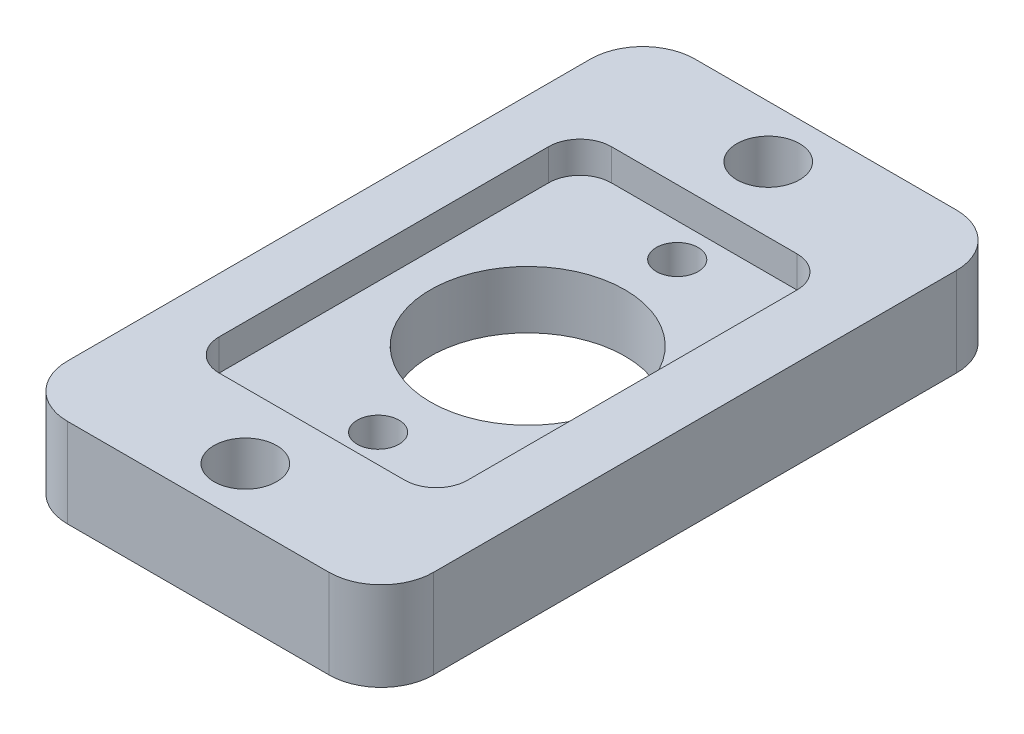
SolidWorks part; units mm, degrees
ref_plane "Front Plane" through (0, 0, 0) normal (0, 0, 1) x (1, 0, 0)
ref_plane "Top Plane" through (0, 0, 0) normal (0, 1, 0) x (1, 0, 0)
ref_plane "Right Plane" through (0, 0, 0) normal (1, 0, 0) x (0, 0, -1)
sketch "Sketch1" plane through (0, 0, 0) normal (0, 1, 0) x (1, 0, 0)
  line L1 (2, 0) -> (12, 0)
  line L2 (0, -2) -> (0, -22)
  line L3 (2, -24) -> (12, -24)
  line L4 (14, -2) -> (14, -22)
  arc A0 (0, -22) -> (2, -24) centre (2, -22) ccw
  arc A1 (12, -24) -> (14, -22) centre (12, -22) ccw
  arc A2 (12, 0) -> (14, -2) centre (12, -2) cw
  arc A3 (2, 0) -> (0, -2) centre (2, -2) ccw
  point P7 (0, -24)
  point P12 (14, 0)
  point P15 (0, 0)
  dimension "D3" = 2
  dimension "D1" = 14
  dimension "D2" = 24
extrude "Boss-Extrude1" add sketch "Sketch1" along normal blind 3.4
sketch "Sketch2" plane through (0, 3.4, 0) normal (0, 1, 0) x (1, 0, 0)
  line L0 (12, 0) -> (2, 0) construction
  line L1 (3.3, -4.5) -> (10.4, -4.5)
  line L2 (2.1, -5.7) -> (2.1, -18.3)
  line L3 (3.3, -19.5) -> (10.4, -19.5)
  line L4 (11.6, -5.7) -> (11.6, -18.3)
  line L5 (14, -22) -> (14, -2) construction
  arc A0 (2.1, -18.3) -> (3.3, -19.5) centre (3.3, -18.3) ccw
  arc A1 (10.4, -19.5) -> (11.6, -18.3) centre (10.4, -18.3) ccw
  arc A2 (10.4, -4.5) -> (11.6, -5.7) centre (10.4, -5.7) cw
  arc A3 (3.3, -4.5) -> (2.1, -5.7) centre (3.3, -5.7) ccw
  point P4 (6.85, -4.5)
  point P9 (2.1, -19.5)
  point P14 (11.6, -4.5)
  point P17 (2.1, -4.5)
  dimension "D4" = 1.2
  dimension "D1" = 9.5
  dimension "D2" = 15
  dimension "D3" = 4.5
  dimension "D5" = 2.4
extrude "Cut-Extrude1" cut sketch "Sketch2" against normal blind 1.2
sketch "Sketch3" plane through (0, 2.2, 0) normal (0, 1, 0) x (1, 0, 0)
  line L0 (11.6, -18.3) -> (11.6, -5.7) construction
  line L2 (3.3, -19.5) -> (10.4, -19.5) construction
  circle A0 centre (7.1, -11.5) radius 3.72
  circle A1 centre (7.1, -5.78) radius 0.8
  circle A2 centre (7.1, -17.22) radius 0.8
  point P10 (0, 0)
  dimension "D1" = 7.44
  dimension "D4" = 2
  dimension "D2" = 4.5
  dimension "D3" = 8
  dimension "D5" = 2
extrude "Cut-Extrude2" cut sketch "Sketch3" against normal through all
sketch "Sketch4" plane through (0, 3.4, 0) normal (0, 1, 0) x (1, 0, 0)
  line L0 (0, -12) -> (25.4035, -12) construction
  line L1 (0, -2) -> (0, -22) construction
  line L2 (12, 0) -> (2, 0) construction
  circle A0 centre (6.8, -2) radius 1.2
  circle A2 centre (6.8, -22) radius 1.2
  point P10 (0, -3.4611)
  point P11 (0, -3.9254)
  dimension "D1" = 2
  dimension "D2" = 6.8
extrude "Cut-Extrude3" cut sketch "Sketch4" against normal through all
